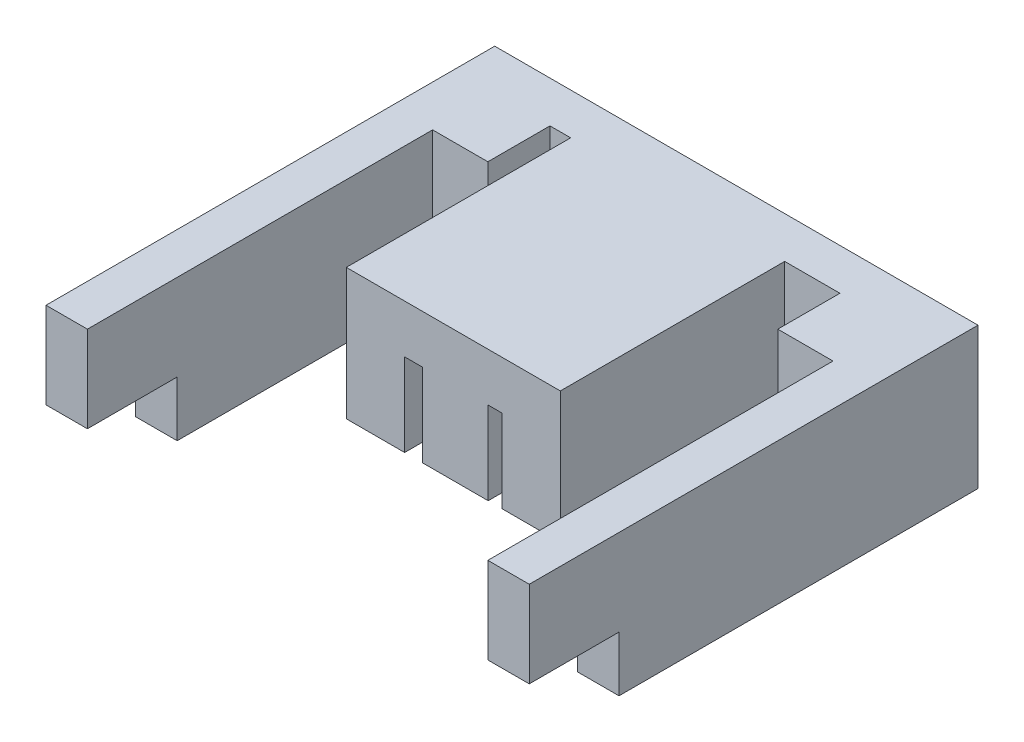
SolidWorks part; units mm, degrees
material "PBT General Purpose"
ref_plane "Front Plane" through (0, 0, 0) normal (0, 0, 1) x (1, 0, 0)
ref_plane "Top Plane" through (0, 0, 0) normal (0, 1, 0) x (1, 0, 0)
ref_plane "Right Plane" through (0, 0, 0) normal (1, 0, 0) x (0, 0, -1)
sketch "Sketch1" plane through (0, 0, 0) normal (0, 1, 0) x (1, 0, 0)
  line L0 (29, -32.5) -> (35, -32.5)
  line L1 (-35, 32.5) -> (35, 32.5)
  line L2 (-35, 32.5) -> (-35, -32.5)
  line L3 (-35, -32.5) -> (-29, -32.5)
  line L4 (35, 32.5) -> (35, -32.5)
  line L5 (-29, 26.5) -> (29, 26.5)
  line L6 (-29, 26.5) -> (-29, -32.5)
  line L8 (29, 26.5) -> (29, -32.5)
  point P8 (0, 26.5)
  point P10 (-35, 0)
  dimension "D1" = 70
  dimension "D2" = 65
  dimension "D3" = 6
  dimension "D4" = 6
  dimension "D5" = 6
extrude "Boss-Extrude1" add sketch "Sketch1" along normal blind 20.5
sketch "Sketch2" plane through (0, 0, 0) normal (0, -1, 0) x (1, 0, 0)
  line L0 (35, 32.5) -> (35, -32.5) construction
  line L1 (29, 32.5) -> (35, 32.5)
  line L2 (29, 32.5) -> (29, 19.5)
  line L3 (29, 19.5) -> (35, 19.5)
  line L4 (35, 32.5) -> (35, 19.5)
  line L5 (0, -1000) -> (0, 49000) construction
  line L6 (-29, -26.5) -> (29, -26.5) construction
  line L7 (-12.5, -26.5) -> (12.5, -26.5)
  line L8 (-12.5, -26.5) -> (-12.5, -32.5)
  line L9 (-12.5, -32.5) -> (12.5, -32.5)
  line L10 (12.5, -26.5) -> (12.5, -32.5)
  line L11 (35, -32.5) -> (-35, -32.5) construction
  line L12 (-29, 19.5) -> (-35, 19.5)
  line L13 (-35, 32.5) -> (-35, 19.5)
  line L14 (-29, 32.5) -> (-35, 32.5)
  line L15 (-29, 32.5) -> (-29, 19.5)
  point P18 (0, -26.5)
  point P19 (0, -26.5)
  dimension "D1" = 13
  dimension "D2" = 25
extrude "Cut-Extrude1" cut sketch "Sketch2" against normal blind 8
sketch "Sketch3" plane through (0, 20.5, 0) normal (0, 1, 0) x (1, 0, 0)
  line L0 (-29, -32.5) -> (-29, 26.5) construction
  line L1 (-14, 21) -> (9, 21)
  line L2 (-14, 21) -> (-14, -2)
  line L3 (-14, -2) -> (9, -2)
  line L4 (9, 21) -> (9, -2)
  line L5 (-29, 26.5) -> (29, 26.5) construction
  dimension "D1" = 23
  dimension "D2" = 23
  dimension "D3" = 15
  dimension "D4" = 5.5
extrude "Boss-Extrude2" add sketch "Sketch3" against normal offset from surface (7 mm away) 13.5 separate body up to face at (-25.5, 0, -13.1667)
sketch "Sketch4" plane through (0, 20.5, 0) normal (0, 1, 0) x (1, 0, 0)
  line L0 (-18, 26.5) -> (-18, -6)
  line L1 (-29, 26.5) -> (29, 26.5) construction
  line L2 (-18, -6) -> (13, -6)
  line L3 (13, -6) -> (13, 26.5)
  line L4 (-14, 21) -> (-14, -2)
  line L5 (-14, -2) -> (9, -2)
  line L6 (9, -2) -> (9, 21)
  line L7 (9, 21) -> (-14, 21)
  line L8 (-14, 21) -> (-14, -2)
  line L9 (-14, -2) -> (9, -2)
  line L10 (9, -2) -> (9, 21)
  line L11 (9, 21) -> (-14, 21)
  line L12 (13, 26.5) -> (-18, 26.5)
  line M12 (-29, 26.5) -> (29, 26.5)
  dimension "D2" = 4
  dimension "D3" = 4
  dimension "D4" = 4
  dimension "D1" = 0
extrude "Boss-Extrude4" add sketch "Sketch4" against normal offset from surface (19 mm away) 12 contours L2 L3 L0 L11 L10 L9 L8 M12 region at (-2.5, 20.5, -26.0509) up to face at (-2.5, 13.5, -9.5) offset beyond the face yes
sketch "Sketch5" plane through (0, 1.5, 0) normal (0, -1, 0) x (1, 0, 0)
  line L0 (-14, -21) -> (9, -21) construction
  line L1 (-6.95, -21) -> (-9.55, -21)
  line L2 (-6.95, -21) -> (-6.95, -26.5)
  line L3 (-6.95, -26.5) -> (-9.55, -26.5)
  line L4 (-9.55, -21) -> (-9.55, -26.5)
  line L5 (12.5, -26.5) -> (-12.5, -26.5) construction
  line L6 (9, 2) -> (-14, 2) construction
  line L7 (-9.55, 2) -> (-6.95, 2)
  line L8 (-9.55, 2) -> (-9.55, 6)
  line L9 (-9.55, 6) -> (-6.95, 6)
  line L10 (-6.95, 2) -> (-6.95, 6)
  line L11 (13, 6) -> (-18, 6) construction
  line L12 (-18, 6) -> (-18, -26.5) construction
  line L13 (-18, 2) -> (-14, 2)
  line L14 (-18, 2) -> (-18, -13)
  line L15 (-18, -13) -> (-14, -13)
  line L16 (-14, 2) -> (-14, -13)
  line L17 (-14, 2) -> (-14, -21) construction
  line L18 (9, 2) -> (-14, 2) construction
  line L19 (2.55, 6) -> (4.55, 6)
  line L20 (2.55, 6) -> (2.55, 2)
  line L21 (2.55, 2) -> (4.55, 2)
  line L22 (4.55, 6) -> (4.55, 2)
  line L23 (-14, 2) -> (-14, -21) construction
  dimension "D1" = 2
  dimension "D2" = 9.5
  dimension "D3" = 15
  dimension "D4" = 2.6
  dimension "D5" = 4.45
extrude "Cut-Extrude2" cut sketch "Sketch5" against normal up to surface (12 mm away) up to face at (-2.5, 13.5, -9.5)
sketch "Sketch7" plane through (0, 20.5, 0) normal (0, 1, 0) x (1, 0, 0)
  line L1 (29, 26.5) -> (21, 26.5)
  line L2 (29, 26.5) -> (29, 17.5)
  line L3 (29, 17.5) -> (21, 17.5)
  line L4 (21, 26.5) -> (21, 17.5)
  line L5 (-29, 26.5) -> (-21, 26.5)
  line L6 (-29, 26.5) -> (-29, 17.5)
  line L7 (-29, 17.5) -> (-21, 17.5)
  line L8 (-21, 26.5) -> (-21, 17.5)
  dimension "D1" = 8
  dimension "D2" = 9
  dimension "D3" = 9
  dimension "D4" = 8
extrude "Boss-Extrude5" add sketch "Sketch7" against normal up to surface (20.5 mm away) up to face at (25.5, 0, -13.1667)
sketch "Sketch8" plane through (0, 0, -32.5) normal (0, 0, -1) x (-1, 0, 0)
  line L0 (-35, 20.5) -> (-35, 0) construction
  line L1 (35, 20.5) -> (35, 0) construction
  line L2 (12.5, 0) -> (35, 0) construction
  line L3 (-35, 0) -> (-12.5, 0) construction
  circle A0 centre (-25, 11) radius 2.1
  circle A1 centre (25, 11) radius 2.1
  dimension "D1" = 4.2
  dimension "D2" = 4.2
  dimension "D5" = 11
  dimension "D6" = 11
  dimension "D3" = 10
  dimension "D4" = 10
extrude "Cut-Extrude4" cut sketch "Sketch8" against normal blind 10
equation "\"body_height\"= 41mm"
equation "\"D1@Boss-Extrude1\"=\"body_height\" / 2"
equation "\"D1@Boss-Extrude2\"=12+1.5"
